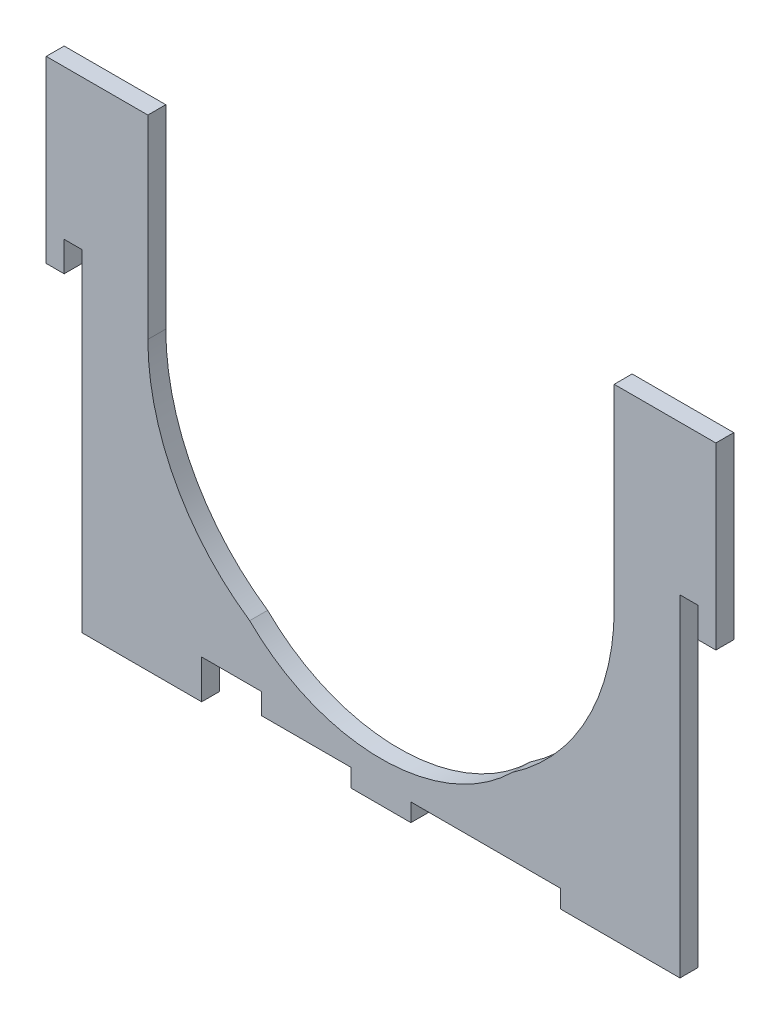
SolidWorks part; units mm, degrees
ref_plane "Front" through (0, 0, 0) normal (0, 0, 1) x (1, 0, 0)
ref_plane "Top" through (0, 0, 0) normal (0, 1, 0) x (1, 0, 0)
ref_plane "Right" through (0, 0, 0) normal (1, 0, 0) x (0, 0, -1)
sketch "Sketch1" plane through (0, 0, 0) normal (0, 0, 1) x (1, 0, 0)
  line L0 (-178, 90) -> (-178, 155)
  line L1 (0, 0) -> (-200, 0)
  line L2 (0, 0) -> (0, 155)
  line L3 (0, 155) -> (-22, 155)
  line L4 (-200, 0) -> (-200, 155)
  line L5 (-100, 155) -> (-100, 70) construction
  line L6 (-22, 90) -> (-22, 155)
  line L7 (-178, 155) -> (-200, 155)
  line L8 (-178, 155) -> (-22, 155) construction
  arc A0 (-178, 90) -> (-143.9432, 25.5563) centre (-100, 90) ccw
  arc A1 (-143.9432, 25.5563) -> (-56.0568, 25.5562) centre (-100, 70) ccw
  arc A2 (-56.0568, 25.5562) -> (-22, 90) centre (-100, 90) ccw
  dimension "D3" = 156
  dimension "D4" = 125
  dimension "D1" = 155
  dimension "D2" = 200
  dimension "D5" = 20
  dimension "D6" = 90
extrude "Boss-Extrude1" add sketch "Sketch1" along normal blind 6
sketch "Sketch3" plane through (0, 0, 6) normal (0, 0, 1) x (1, 0, 0)
  line L2 (-200, 155) -> (-200, 105)
  line L3 (-200, 105) -> (-206, 105)
  line L5 (-200, 155) -> (-212, 155)
  line L6 (-206, 105) -> (-206, 95)
  line L7 (-206, 95) -> (-212, 95)
  line L8 (-212, 155) -> (-212, 95)
  point P8 (-206, 156.4385)
  point P9 (0, 0)
  dimension "D1" = 50
  dimension "D2" = 6
  dimension "D3" = 12
  dimension "D4" = 10
extrude "Boss-Extrude2" add sketch "Sketch3" against normal blind 6
ref_plane "Plane1" through (-100, 0, 0) normal (-1, 0, 0) x (0, 0, 1)
mirror "Mirror1" about plane through (-100, 0, 0) normal (-1, 0, 0) of "Boss-Extrude2"
sketch "Sketch4" plane through (0, 0, 6) normal (0, 0, 1) x (1, 0, 0)
  line L0 (-200, 0) -> (0, 0) construction
  line L1 (-200, 0) -> (-160, 0)
  line L2 (-200, 0) -> (-200, -6)
  line L3 (-200, -6) -> (-160, -6)
  line L4 (-160, 0) -> (-160, -6)
  line L5 (-110, 0) -> (-90, 0)
  line L6 (-110, 0) -> (-110, -6)
  line L7 (-110, -6) -> (-90, -6)
  line L8 (-90, 0) -> (-90, -6)
  line L10 (0, 0) -> (-40, 0)
  line L11 (0, 0) -> (0, -6)
  line L12 (0, -6) -> (-40, -6)
  line L13 (-40, 0) -> (-40, -6)
  point P16 (-100, 0)
  point P17 (-100, 0)
  dimension "D1" = 6
  dimension "D2" = 40
  dimension "D3" = 20
extrude "Boss-Extrude3" add sketch "Sketch4" against normal blind 6
sketch "Sketch5" plane through (0, 0, 6) normal (0, 0, 1) x (1, 0, 0)
  line L1 (-160, 0) -> (-140, 0)
  line L2 (-160, 0) -> (-160, 7)
  line L3 (-160, 7) -> (-140, 7)
  line L4 (-140, 0) -> (-140, 7)
  dimension "D1" = 7
  dimension "D2" = 20
extrude "Cut-Extrude1" cut sketch "Sketch5" against normal blind 10
